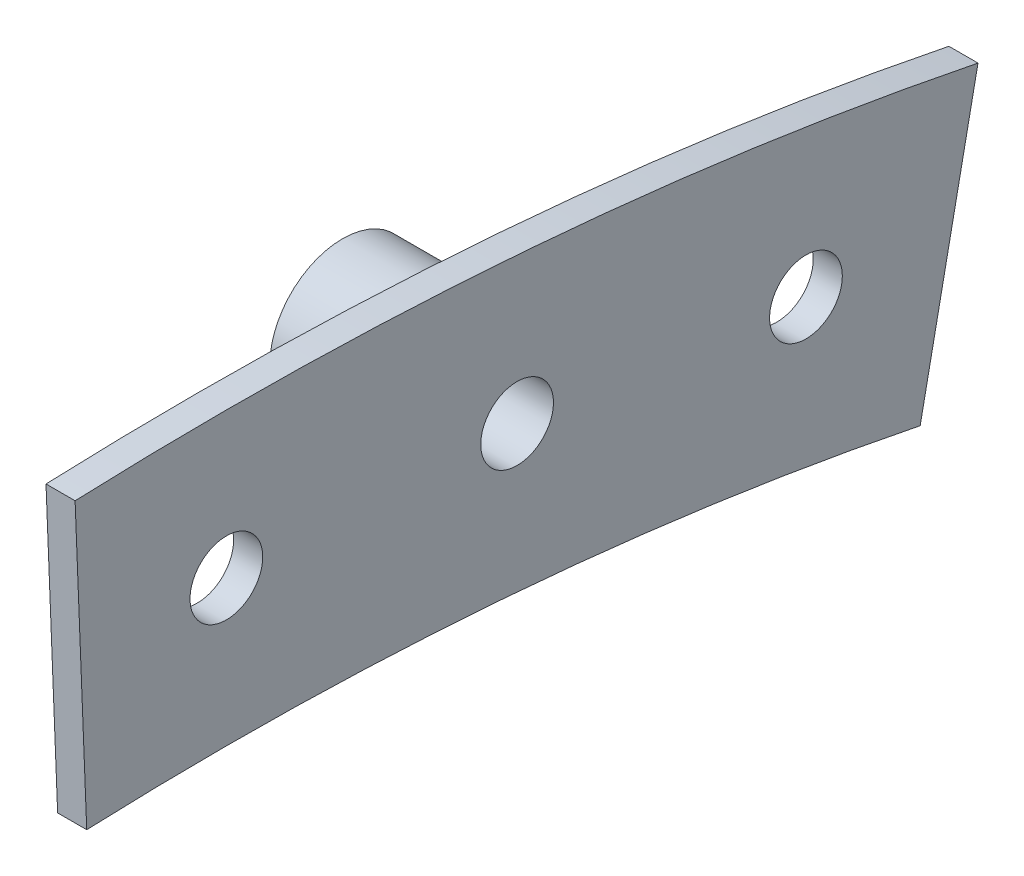
SolidWorks part; units mm, degrees
ref_plane "Front Plane" through (0, 0, 0) normal (0, 0, 1) x (1, 0, 0)
ref_plane "Top Plane" through (0, 0, 0) normal (0, 1, 0) x (1, 0, 0)
ref_plane "Right Plane" through (0, 0, 0) normal (1, 0, 0) x (0, 0, -1)
sketch "Sketch1" plane through (0, 0, 0) normal (1, 0, 0) x (0, 0, -1)
  line L0 (-12.1896, 304.5562) -> (-13.2054, 329.9358)
  line L1 (0, 317.5) -> (0, 0) construction
  line L2 (60.568, 298.7215) -> (65.6153, 323.615)
  line L3 (65.6153, 323.615) -> (0, 0) construction
  arc A0 (0, 317.5) -> (50.5969, 313.4425) centre (0, 0) cw
  circle A1 centre (0, 317.5) radius 3.175
  circle A2 centre (25.3797, 316.484) radius 3.175
  circle A3 centre (50.5969, 313.4425) radius 3.175
  arc A4 (-12.1896, 304.5562) -> (60.568, 298.7215) centre (0, 0) cw
  arc A5 (-13.2054, 329.9358) -> (65.6153, 323.615) centre (0, 0) cw
  point P5 (25.3797, 316.484)
  point P13 (-12.6975, 317.246)
  point P14 (-12.1896, 304.5562)
  point P15 (63.0916, 311.1683)
  dimension "D1" = 317.5
  dimension "D3" = 6.35
  dimension "D4" = 6.35
  dimension "D5" = 6.35
  dimension "D6" = 304.8
  dimension "D7" = 25.4
  dimension "D8" = 12.6975
  dimension "D2" = 25.4
  dimension "D9" = 12.7
extrude "Boss-Extrude1" add sketch "Sketch1" along normal blind 2.54 contours A5 L0 A4 L2 A3 A2 A1 region at (0, 317.2799, 11.8494)
sketch "Sketch2" plane through (0, 0, 0) normal (-1, 0, 0) x (0, 0, 1)
  circle A0 centre (-25.3797, 316.484) radius 6.35
  dimension "D1" = 12.7
extrude "Boss-Extrude2" add sketch "Sketch2" along normal blind 12.7 contours A0
sketch "Sketch4" plane through (0, 0, 0) normal (1, 0, 0) x (0, 0, -1)
  circle A0 centre (25.3797, 316.484) radius 3.175
extrude "Cut-Extrude1" cut sketch "Sketch4" against normal blind 6.35
